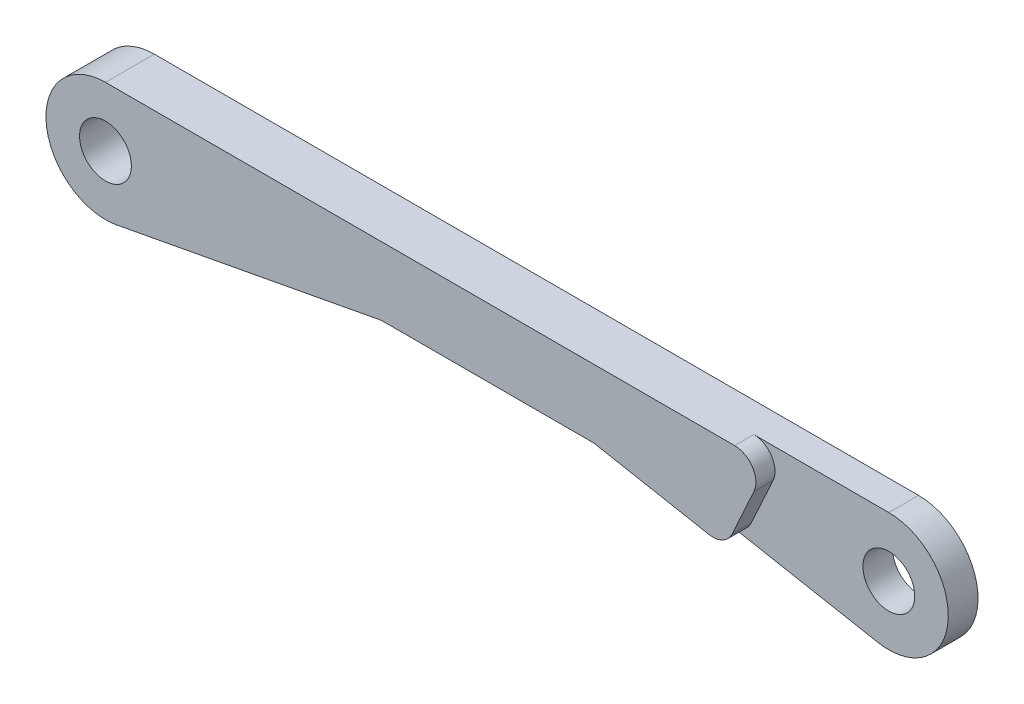
SolidWorks part; units mm, degrees
ref_plane "前视基准面" through (0, 0, 0) normal (0, 0, 1) x (1, 0, 0)
ref_plane "上视基准面" through (0, 0, 0) normal (0, 1, 0) x (1, 0, 0)
ref_plane "右视基准面" through (0, 0, 0) normal (1, 0, 0) x (0, 0, -1)
sketch "草图1" plane through (0, 0, 0) normal (0, 0, 1) x (1, 0, 0)
  line L0 (0, 0) -> (-179.89, 0) construction
  line L1 (-89.945, 0) -> (-89.945, 14)
  line L2 (-160.0649, 14) -> (-19.8251, 14)
  line L3 (-160.0649, 14) -> (-179.89, 14)
  line L4 (-19.8251, 14) -> (0, 14)
  line L5 (-179.89, 0) -> (-170.2307, 2.5882)
  line L7 (-89.6593, 2.5882) -> (-2.5833, -13.7596)
  line L8 (0, 0) -> (-9.6593, 2.5882)
  line L9 (-170.2307, 2.5882) -> (-9.6593, 2.5882)
  line L10 (-177.3067, -13.7596) -> (-90.2307, 2.5882)
  circle A0 centre (0, 0) radius 6.1
  circle A1 centre (-179.89, 0) radius 6.1
  circle A2 centre (-179.89, 0) radius 14
  circle A3 centre (0, 0) radius 14
  point P10 (-89.945, 14)
  dimension "D1" = 28
  dimension "D2" = 28
  dimension "D7" = 12.2
  dimension "D8" = 12.2
  dimension "D3" = 179.89
  dimension "D4" = 15
  dimension "D5" = 15
  dimension "D6" = 10
  dimension "D9" = 80
  dimension "D10" = 80
extrude "凸台-拉伸2" add sketch "草图1" along normal blind 10 contours A2 L0 A1 L5 | L0 A2 L5 A1 | L10 L0 A2 | L0 L10 L9 L5 A2 | A2 L5 L9 L1 L2 L3 | A3 L4 L2 L1 L9 L8 | A0 L0 A3 L8 | L0 A0 L8 A3 | L0 A3 L8 L9 L7 | A3 L0 L7 region at (-169.4206, -8.6868, 0) region at (-131.4319, 1.338, 0) region at (-146.8737, -4.2674, 0) region at (-169.6563, 1.1975, 0) region at (-129.8116, 8.4149, 0) region at (-48.4581, 1.338, 0) region at (-33.0163, -4.2674, 0) region at (-50.0784, 8.4149, 0) region at (-10.2337, 1.1975, 0) region at (-10.05, -0.396, 0)
sketch "草图2" plane through (0, 0, 0) normal (0, 0, -1) x (-1, 0, 0)
  line L0 (14, 14) -> (14, -11.6162)
  line L4 (2.5833, -13.7596) -> (89.6593, 2.5882)
  line L5 (89.6593, 2.5882) -> (90.2307, 2.5882)
  line L6 (90.2307, 2.5882) -> (177.3067, -13.7596)
  line L7 (179.89, 14) -> (0, 14)
  line L8 (2.5833, -13.7596) -> (89.6593, 2.5882)
  line L9 (89.6593, 2.5882) -> (90.2307, 2.5882)
  line L10 (90.2307, 2.5882) -> (177.3067, -13.7596)
  line L11 (179.89, 14) -> (0, 14)
  circle A0 centre (0, 0) radius 14
  circle A1 centre (0, 0) radius 8
  arc A3 (177.3067, -13.7596) -> (179.89, 14) centre (179.89, 0) ccw
  arc A4 (0, 14) -> (2.5833, -13.7596) centre (0, 0) ccw
  arc A5 (177.3067, -13.7596) -> (179.89, 14) centre (179.89, 0) ccw
  arc A6 (0, 14) -> (2.5833, -13.7596) centre (0, 0) ccw
  circle A7 centre (0, 0) radius 6.1 construction
  circle A8 centre (0, 0) radius 6.1
  dimension "D2" = 16
  dimension "D1" = 0
sketch "草图4" plane through (0, 0, 10) normal (0, 0, 1) x (1, 0, 0)
  line L4 (-89.6593, 2.5882) -> (-2.5833, -13.7596)
  line L5 (0, 14) -> (-179.89, 14)
  line L6 (-177.3067, -13.7596) -> (-90.2307, 2.5882)
  line L7 (-90.2307, 2.5882) -> (-89.6593, 2.5882)
  line L8 (-89.6593, 2.5882) -> (-2.5833, -13.7596)
  line L9 (0, 14) -> (-179.89, 14)
  line L10 (-177.3067, -13.7596) -> (-90.2307, 2.5882)
  line L11 (-90.2307, 2.5882) -> (-89.6593, 2.5882)
  circle A0 centre (-179.89, 0) radius 14
  arc A3 (-2.5833, -13.7596) -> (0, 14) centre (0, 0) ccw
  arc A4 (-179.89, 14) -> (-177.3067, -13.7596) centre (-179.89, 0) ccw
  arc A5 (-2.5833, -13.7596) -> (0, 14) centre (0, 0) ccw
  arc A6 (-179.89, 14) -> (-177.3067, -13.7596) centre (-179.89, 0) ccw
  line M7 (-89.6593, 2.5882) -> (-2.5833, -13.7596)
  arc M8 (-2.5833, -13.7596) -> (0, 14) centre (0, 0) ccw
  line M9 (0, 14) -> (-179.89, 14)
  line M11 (-177.3067, -13.7596) -> (-90.2307, 2.5882)
  line M12 (-90.2307, 2.5882) -> (-89.6593, 2.5882)
  circle M13 centre (0, 0) radius 6.1
  dimension "D1" = 0
extrude "切除-拉伸3" cut sketch "草图4" against normal blind 3 contours A0 M11 M12 M7 M8 M9 M13 region at (-76.9196, 3.6202, 10)
sketch "草图5" plane through (0, 0, 10) normal (0, 0, 1) x (1, 0, 0)
  circle A1 centre (-179.89, 0) radius 14
  circle A2 centre (-179.89, 0) radius 14
  dimension "D1" = 0
extrude "切除-拉伸4" cut sketch "草图5" against normal blind 0.5
sketch "草图7" plane through (0, 0, 9.5) normal (0, 0, 1) x (1, 0, 0)
  circle A0 centre (-179.89, 0) radius 6.1 construction
  circle A1 centre (-179.89, 0) radius 14
  circle A2 centre (-179.89, 0) radius 14
  circle A3 centre (-179.89, 0) radius 6.1
  dimension "D1" = 0
extrude "凸台-拉伸3" add sketch "草图7" along normal blind 2
sketch "草图8" plane through (0, 0, 7) normal (0, 0, 1) x (1, 0, 0)
  line L0 (-114.945, -2.0517) -> (-64.945, -2.0517)
  line L4 (-177.3067, -13.7596) -> (-90.2307, 2.5882)
  line L5 (-90.2307, 2.5882) -> (-89.6593, 2.5882)
  line L6 (-89.6593, 2.5882) -> (-2.5833, -13.7596)
  line L7 (0, 14) -> (-179.89, 14)
  line L8 (-177.3067, -13.7596) -> (-90.2307, 2.5882)
  line L9 (-90.2307, 2.5882) -> (-89.6593, 2.5882)
  line L10 (-89.6593, 2.5882) -> (-2.5833, -13.7596)
  line L11 (0, 14) -> (-179.89, 14)
  arc A2 (-177.3067, -13.7596) -> (-179.89, 14) centre (-179.89, 0) ccw
  arc A3 (-2.5833, -13.7596) -> (0, 14) centre (0, 0) ccw
  arc A4 (-177.3067, -13.7596) -> (-179.89, 14) centre (-179.89, 0) ccw
  arc A5 (-2.5833, -13.7596) -> (0, 14) centre (0, 0) ccw
  line M9 (-177.3067, -13.7596) -> (-90.2307, 2.5882)
  line M10 (-90.2307, 2.5882) -> (-89.6593, 2.5882)
  line M11 (-89.6593, 2.5882) -> (-2.5833, -13.7596)
  dimension "D2" = 50
  dimension "D1" = 0
extrude "凸台-拉伸4" add sketch "草图8" against normal through all contours L0 M9 M11 M10 region at (-89.945, -0.4876, 7)
sketch "草图9" plane through (0, 0, 7) normal (0, 0, 1) x (1, 0, 0)
  line L0 (-24, 14) -> (-34, -7.8614)
  line L2 (-2.5833, -13.7596) -> (-89.6593, 2.5882) construction
  line L3 (-14, 14) -> (-14, -11.6162) construction
  line L4 (-177.3067, -13.7596) -> (-114.945, -2.0517)
  line L5 (-114.945, -2.0517) -> (-64.945, -2.0517)
  line L6 (-64.945, -2.0517) -> (-2.5833, -13.7596)
  line L7 (0, 14) -> (-179.89, 14)
  line L8 (-177.3067, -13.7596) -> (-114.945, -2.0517)
  line L9 (-114.945, -2.0517) -> (-64.945, -2.0517)
  line L10 (-64.945, -2.0517) -> (-2.5833, -13.7596)
  line L11 (0, 14) -> (-179.89, 14)
  circle A1 centre (0, 0) radius 6.1 construction
  circle A2 centre (0, 0) radius 6.1
  arc A3 (-177.3067, -13.7596) -> (-179.89, 14) centre (-179.89, 0) ccw
  arc A4 (-2.5833, -13.7596) -> (0, 14) centre (0, 0) ccw
  arc A5 (-177.3067, -13.7596) -> (-179.89, 14) centre (-179.89, 0) ccw
  arc A6 (-2.5833, -13.7596) -> (0, 14) centre (0, 0) ccw
  point P2 (-30.143, -8.5855)
  arc M7 (-179.89, 14) -> (-177.3067, -13.7596) centre (-179.89, 0) cw
  line M8 (-177.3067, -13.7596) -> (-114.945, -2.0517)
  line M9 (-114.945, -2.0517) -> (-64.945, -2.0517)
  line M10 (-64.945, -2.0517) -> (-2.5833, -13.7596)
  dimension "D1" = 10
  dimension "D3" = 20
  dimension "D2" = 0
extrude "凸台-拉伸5" add sketch "草图9" along normal through all contours L11 M7 M8 M9 M10 region at (-101.5047, 4.5446, 7)
fillet "圆角1" radius 5 2 edges at (-34, -7.8614, 9.25) (-24, 14, 9.25)
